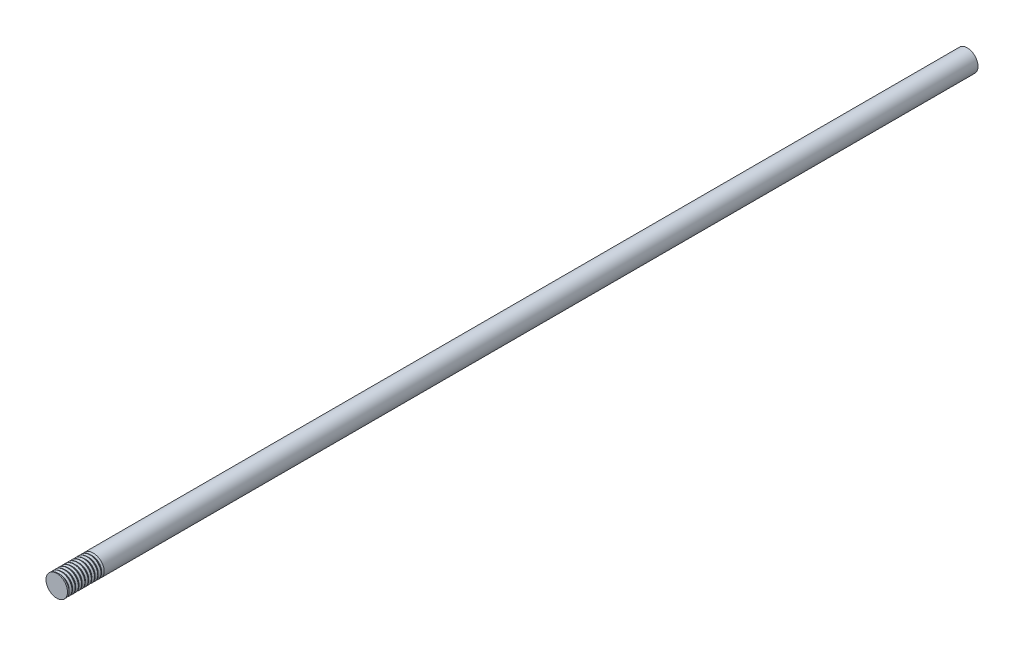
SolidWorks part; units mm, degrees
ref_plane "Alzado" through (0, 0, 0) normal (0, 0, 1) x (1, 0, 0)
ref_plane "Planta" through (0, 0, 0) normal (0, 1, 0) x (1, 0, 0)
ref_plane "Vista lateral" through (0, 0, 0) normal (1, 0, 0) x (0, 0, -1)
sketch "Croquis1" plane through (0, 0, 0) normal (0, 0, 1) x (1, 0, 0)
  circle A0 centre (0, 0) radius 1.5
  dimension "D1" = 3
extrude "Saliente-Extruir1" add sketch "Croquis1" along normal blind 127
cosmetic thread "Rosca cosmética1" parameters "D2"=2.439
thread "Rosca1" pitch 0.45 method cut profile "Perfil de rosca1" start angle 0, offset 0, length 5, pitch 0.45, diameter 3
ref_plane "Plano1" through (-1.5, 0, 127) normal (0, -1, 0) x (-1, 0, 0)
sketch "Perfil de rosca1" plane through (-1.5, 0, 127) normal (0, -1, 0) x (-1, 0, 0)
  line L0 (0, 0) -> (0, 0.45) construction
  line L11 (0, 0) -> (0, 0.3937)
  line L12 (0, 0.3937) -> (-0.2436, 0.2531)
  line L13 (-0.2436, 0.2531) -> (-0.2436, 0.1406)
  line L15 (-0.2436, 0.1406) -> (0, 0)
  line L17 (-0.2436, 0.1969) -> (0, 0.1969) construction
  point P2 (0, 0)
  dimension "Pitch" = 0.45
  dimension "Profile_Angle" = 60
  dimension "Profile_Land" = 0.1125
  dimension "Profile_Height" = 0.2436
equation "\"D1@Saliente-Extruir1\"=240-22.5"
